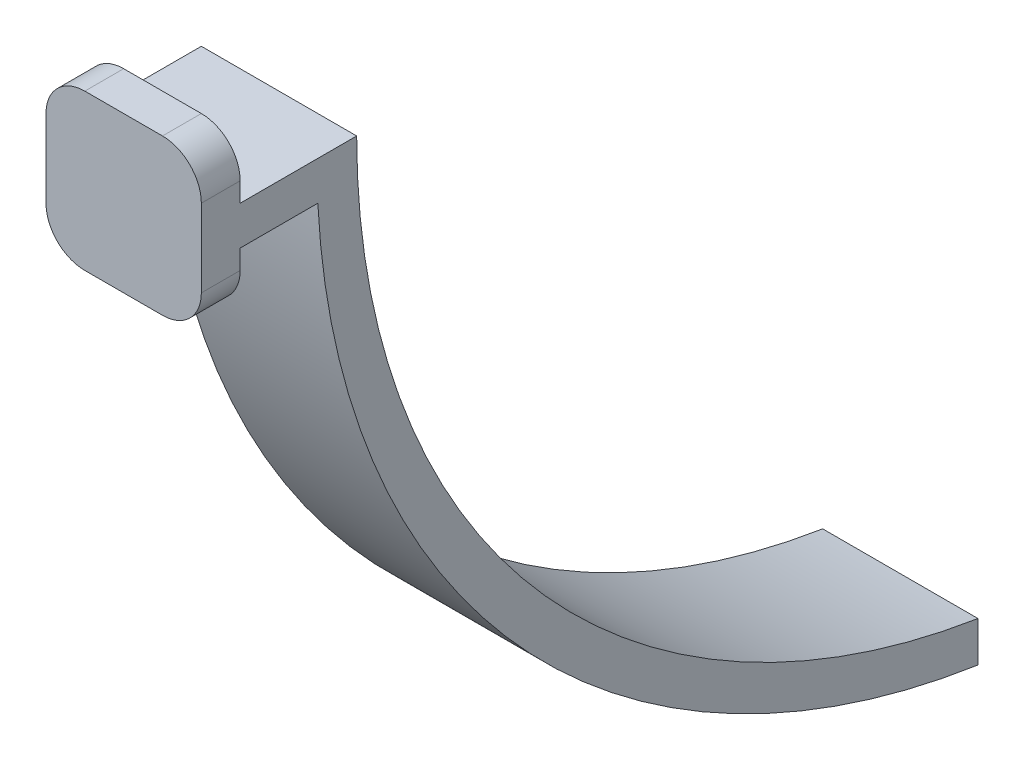
SolidWorks part; units mm, degrees
ref_plane "Front Plane" through (0, 0, 0) normal (0, 0, 1) x (1, 0, 0)
ref_plane "Top Plane" through (0, 0, 0) normal (0, 1, 0) x (1, 0, 0)
ref_plane "Right Plane" through (0, 0, 0) normal (1, 0, 0) x (0, 0, -1)
sketch "Sketch1" plane through (0, 0, 0) normal (1, 0, 0) x (0, 0, -1)
  line L0 (0, 0) -> (0, 25.4)
  line L1 (0, 25.4) -> (6.35, 25.4)
  line L2 (6.35, 25.4) -> (6.35, 15.875)
  line L6 (6.35, 9.525) -> (6.35, 0)
  line L7 (6.35, 0) -> (0, 0)
  line L8 (6.35, 15.875) -> (25.4, 15.875)
  line L9 (6.35, 9.525) -> (19.05, 9.525)
  line L10 (127, -103.2616) -> (127, -109.8486)
  arc A2 (19.05, 9.525) -> (127, -109.8486) centre (146.05, 15.875) ccw
  arc A3 (25.4, 15.875) -> (127, -103.2616) centre (146.05, 15.875) ccw
  point P3 (0, 0)
  point P11 (0, 0)
  point P12 (212.8988, -104.775)
  dimension "D2" = 6.35
  dimension "D3" = 120.65
  dimension "D1" = 6.35
  dimension "D4" = 101.6
  dimension "D5" = 6.35
  dimension "D6" = 25.4
  dimension "D7" = 12.7
extrude "Boss-Extrude1" add sketch "Sketch1" along normal mid plane 25.4
fillet "Fillet2" radius 6.35 4 edges at (-12.7, 0, -3.175) (12.7, 0, -3.175) (12.7, 25.4, -3.175) (-12.7, 25.4, -3.175)
